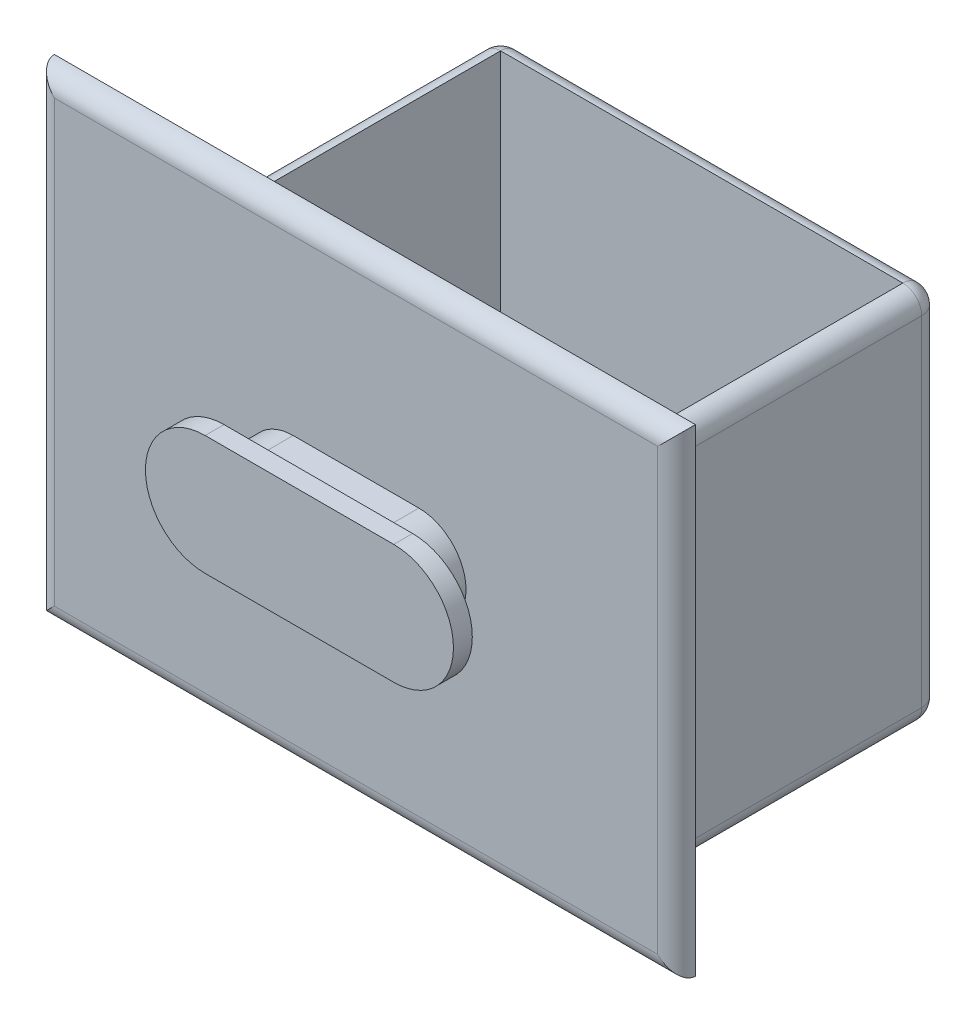
SolidWorks part; units mm, degrees
ref_plane "前视基准面" through (0, 0, 0) normal (0, 0, 1) x (1, 0, 0)
ref_plane "上视基准面" through (0, 0, 0) normal (0, 1, 0) x (1, 0, 0)
ref_plane "右视基准面" through (0, 0, 0) normal (1, 0, 0) x (0, 0, -1)
other "Configuration Table"
sketch "草图1" plane through (0, 0, 0) normal (0, 0, 1) x (1, 0, 0)
  line L1 (-35, -30) -> (35, -30)
  line L2 (-35, -30) -> (-35, 30)
  line L3 (-35, 30) -> (35, 30)
  line L4 (35, -30) -> (35, 30)
  line L5 (-35, -30) -> (35, 30) construction
  line L6 (-35, 30) -> (35, -30) construction
  point P0 (0, 0)
  dimension "D1" = 60
  dimension "D2" = 70
extrude "凸台-拉伸1" add sketch "草图1" along normal blind 55
shell "抽壳1" thickness 3 removed face at (0, 30, 27.5)
sketch "草图2" plane through (0, 0, 55) normal (0, 0, 1) x (1, 0, 0)
  line L0 (-35, -30) -> (35, -30) construction
  line L1 (-51, -30) -> (51, -30)
  line L2 (-51, -30) -> (-51, 46)
  line L3 (-51, 46) -> (51, 46)
  line L4 (51, -30) -> (51, 46)
  line L5 (35, -30) -> (35, 30) construction
  line L6 (-35, 30) -> (-35, -30) construction
  line L7 (35, 30) -> (-35, 30) construction
  dimension "D1" = 16
  dimension "D2" = 16
  dimension "D3" = 16
extrude "凸台-拉伸2" add sketch "草图2" along normal blind 3
fillet "圆角1" radius 3 4 edges at (0, 46, 58) (51, 8, 58) (0, -30, 58) (-51, 8, 58)
fillet "圆角4" radius 3 8 edges at (-35, 0, 0) (0, 30, 0) (35, 0, 0) (0, -30, 0) (-35, 30, 27.5) (35, 30, 27.5) (35, -30, 27.5) (-35, -30, 27.5)
sketch "草图3" plane through (0, 0, 58) normal (0, 0, 1) x (1, 0, 0)
  line L0 (-48, 8) -> (48, 8) construction
  line L1 (-48, 43) -> (-48, -27) construction
  line L2 (48, -27) -> (48, 43) construction
  line L3 (0, 43) -> (0, -27) construction
  line L4 (48, 43) -> (-48, 43) construction
  line L5 (-48, -27) -> (48, -27) construction
  line L6 (-10, 8) -> (10, 8) construction
  line L7 (-10, 15.5) -> (10, 15.5)
  line L8 (-10, 0.5) -> (10, 0.5)
  arc A0 (-10, 15.5) -> (-10, 0.5) centre (-10, 8) ccw
  arc A1 (10, 0.5) -> (10, 15.5) centre (10, 8) ccw
  point P14 (0, 8)
  dimension "D1" = 15
  dimension "D2" = 20
extrude "凸台-拉伸3" add sketch "草图3" along normal blind 6
sketch "草图4" plane through (0, 0, 64) normal (0, 0, 1) x (1, 0, 0)
  line L0 (-17.5, 8) -> (17.5, 8) construction
  line L1 (-15, 8) -> (15, 8) construction
  line L2 (-15, 17.5) -> (15, 17.5)
  line L3 (-15, -1.5) -> (15, -1.5)
  arc A0 (-10, 15.5) -> (-10, 0.5) centre (-10, 8) ccw construction
  arc A1 (10, 0.5) -> (10, 15.5) centre (10, 8) ccw construction
  arc A2 (-15, 17.5) -> (-15, -1.5) centre (-15, 8) ccw
  arc A3 (15, -1.5) -> (15, 17.5) centre (15, 8) ccw
  point P10 (0, 8)
  point P15 (0, 0)
  dimension "D1" = 19
  dimension "D2" = 15
extrude "凸台-拉伸4" add sketch "草图4" along normal blind 3
